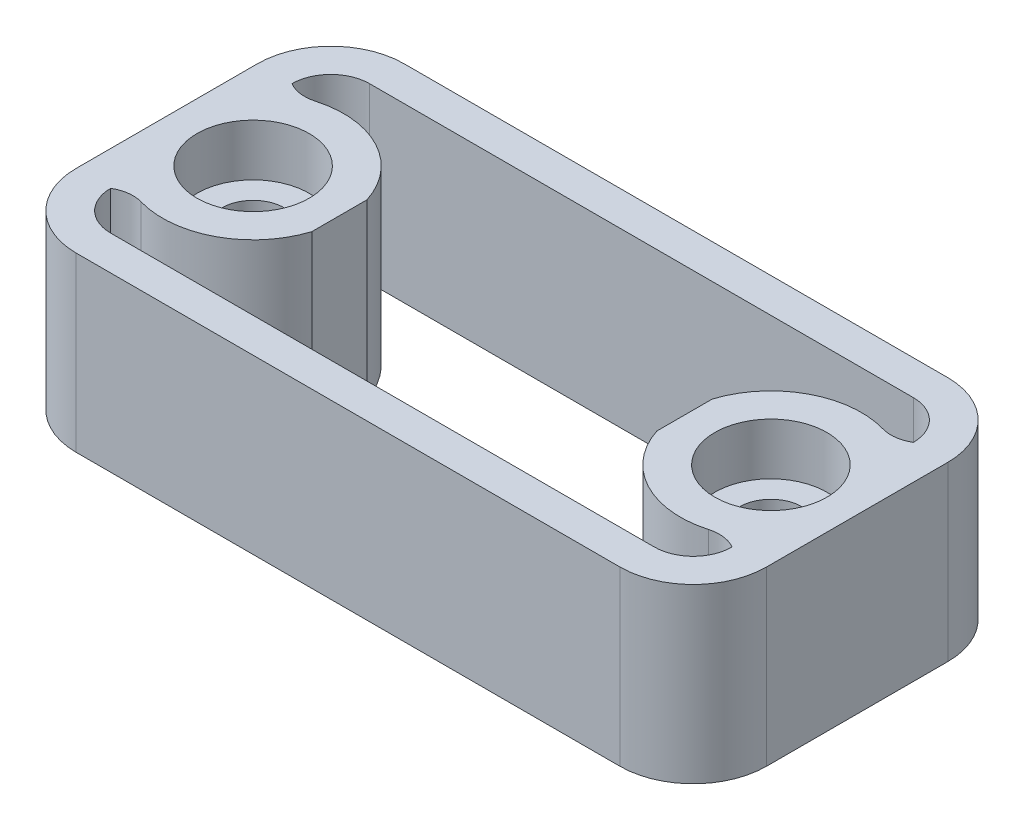
SolidWorks part; units mm, degrees
ref_plane "Front Plane" through (0, 0, 0) normal (0, 0, 1) x (1, 0, 0)
ref_plane "Top Plane" through (0, 0, 0) normal (0, 1, 0) x (1, 0, 0)
ref_plane "Right Plane" through (0, 0, 0) normal (1, 0, 0) x (0, 0, -1)
sketch "Sketch1" plane through (0, 0, 0) normal (0, 1, 0) x (1, 0, 0)
  line L0 (-18, 7.5) -> (18, 7.5)
  line L1 (-20, 9.5) -> (20, 9.5)
  line L2 (-20, 9.5) -> (-20, -9.5)
  line L3 (-20, -9.5) -> (20, -9.5)
  line L4 (20, 9.5) -> (20, -9.5)
  line L5 (-20, 9.5) -> (20, -9.5) construction
  line L6 (-20, -9.5) -> (20, 9.5) construction
  line L7 (18, 7.5) -> (18, -7.5)
  line L8 (-18, -7.5) -> (18, -7.5)
  line L9 (-18, 7.5) -> (-18, -7.5)
  point P0 (0, 0)
  dimension "D1" = 40
  dimension "D2" = 19
  dimension "D3" = 2
extrude "Boss-Extrude1" add sketch "Sketch1" along normal blind 10
fillet "Fillet1" radius 4.25 8 edges at (-20, 5, 9.5) (-20, 5, -9.5) (20, 5, -9.5) (20, 5, 9.5) (-18, 5, 7.5) (18, 5, 7.5) (18, 5, -7.5) (-18, 5, -7.5)
ref_axis "Axis1" through (0, -0.5, 0) along (0, 1, 0)
sketch "Sketch2" plane through (0, 0, 0) normal (0, 1, 0) x (1, 0, 0)
  line L0 (18, -3.25) -> (18, 3.25) construction
  line L1 (-13.75, -7.5) -> (13.75, -7.5) construction
  line L2 (13.75, 7.5) -> (-13.75, 7.5) construction
  line L3 (-18, 3.25) -> (-18, -3.25) construction
  line L4 (18, -3.25) -> (18, 3.25)
  line L5 (-13.75, -7.5) -> (-10, -7.5)
  line L6 (13.75, 7.5) -> (10, 7.5)
  line L7 (-18, 3.25) -> (-18, -3.25)
  line L8 (0, 0) -> (0, -14.9602) construction
  line L9 (-10, 7.5) -> (-10, -7.5)
  line L10 (10, 7.5) -> (10, -7.5)
  line L11 (-10, 7.5) -> (-13.75, 7.5)
  line L12 (10, -7.5) -> (13.75, -7.5)
  arc A0 (18, 3.25) -> (13.75, 7.5) centre (13.75, 3.25) ccw construction
  arc A1 (13.75, -7.5) -> (18, -3.25) centre (13.75, -3.25) ccw construction
  arc A2 (-18, -3.25) -> (-13.75, -7.5) centre (-13.75, -3.25) ccw construction
  arc A3 (-13.75, 7.5) -> (-18, 3.25) centre (-13.75, 3.25) ccw construction
  arc A4 (18, 3.25) -> (13.75, 7.5) centre (13.75, 3.25) ccw
  arc A5 (13.75, -7.5) -> (18, -3.25) centre (13.75, -3.25) ccw
  arc A6 (-18, -3.25) -> (-13.75, -7.5) centre (-13.75, -3.25) ccw
  arc A7 (-13.75, 7.5) -> (-18, 3.25) centre (-13.75, 3.25) ccw
  dimension "D1" = 20
extrude "Boss-Extrude2" add sketch "Sketch2" along normal up to surface (10 mm away) up to face at (0, 10, 0)
hole_wizard "CBORE for M3 SHCS1" positions "Sketch3" profile "Sketch4" counterbore size "M3" standard "ANSI Metric" end condition through all
sketch "Sketch3" plane through (0, 10, 0) normal (0, 1, 0) x (1, 0, 0)
  line L0 (0, 0) -> (0, 13.2527) construction
  point P0 (-15, 0)
  point P2 (15, 0)
  point P19 (0, 0)
sketch "Sketch4" plane through (-15, 10, 0) normal (1, 0, 0) x (0, 0, 1)
  line L0 (0, 0) -> (0, 10)
  line L1 (0, 10) -> (1.8, 10)
  line L3 (1.8, 10) -> (1.8, 3)
  line L4 (1.8, 3) -> (3.25, 3)
  line L5 (3.25, 3) -> (3.25, 0)
  line L7 (3.25, 0) -> (0, 0)
  line L11 (0, -6.35) -> (0, 107.95) construction
  dimension "Thru Hole Dia." = 3.6
  dimension "Thru Hole Depth" = 10
  dimension "C'Bore Dia." = 6.5
  dimension "C'Bore Depth" = 3
sketch "Sketch5" plane through (0, 10, 0) normal (0, 1, 0) x (1, 0, 0)
  line L2 (15.75, 7.5) -> (-15.75, 7.5)
  line L3 (15.75, 7.5) -> (-15.75, 7.5)
  line L5 (-18, 5.25) -> (-18, -5.25)
  line L6 (-18, 5.25) -> (-18, 4.3084)
  line L8 (-18, -4.3084) -> (-18, -5.25)
  line L9 (18, 4.3084) -> (18, 5.25)
  line L10 (18, -5.25) -> (18, 5.25)
  line L11 (-15.75, -7.5) -> (15.75, -7.5)
  line L12 (18, -5.25) -> (18, -4.3084)
  line L13 (-15.75, -7.5) -> (15.75, -7.5)
  circle A2 centre (-15, 0) radius 5.25
  arc A3 (-18, -4.3084) -> (-18, 4.3084) centre (-15, 0) ccw
  arc A5 (-15.75, 7.5) -> (-18, 5.25) centre (-15.75, 5.25) ccw
  arc A6 (-15.75, 7.5) -> (-18, 5.25) centre (-15.75, 5.25) ccw
  circle A11 centre (15, 0) radius 5.25
  arc A12 (18, 5.25) -> (15.75, 7.5) centre (15.75, 5.25) ccw
  arc A13 (15.75, -7.5) -> (18, -5.25) centre (15.75, -5.25) ccw
  arc A14 (-18, -5.25) -> (-15.75, -7.5) centre (-15.75, -5.25) ccw
  arc A15 (18, 5.25) -> (15.75, 7.5) centre (15.75, 5.25) ccw
  arc A16 (15.75, -7.5) -> (18, -5.25) centre (15.75, -5.25) ccw
  arc A17 (-18, -5.25) -> (-15.75, -7.5) centre (-15.75, -5.25) ccw
  arc A18 (18, 4.3084) -> (18, -4.3084) centre (15, 0) ccw
  dimension "D1" = 2
  dimension "D2" = 2
  dimension "D3" = 2
  dimension "D4" = 2
  dimension "D5" = 2
  dimension "D6" = 2
extrude "Cut-Extrude1" cut sketch "Sketch5" against normal through all
fillet "Fillet2" radius 2 4 edges at (18, 5, 4.3084) (18, 5, -4.3084) (-18, 5, -4.3084) (-18, 5, 4.3084)
